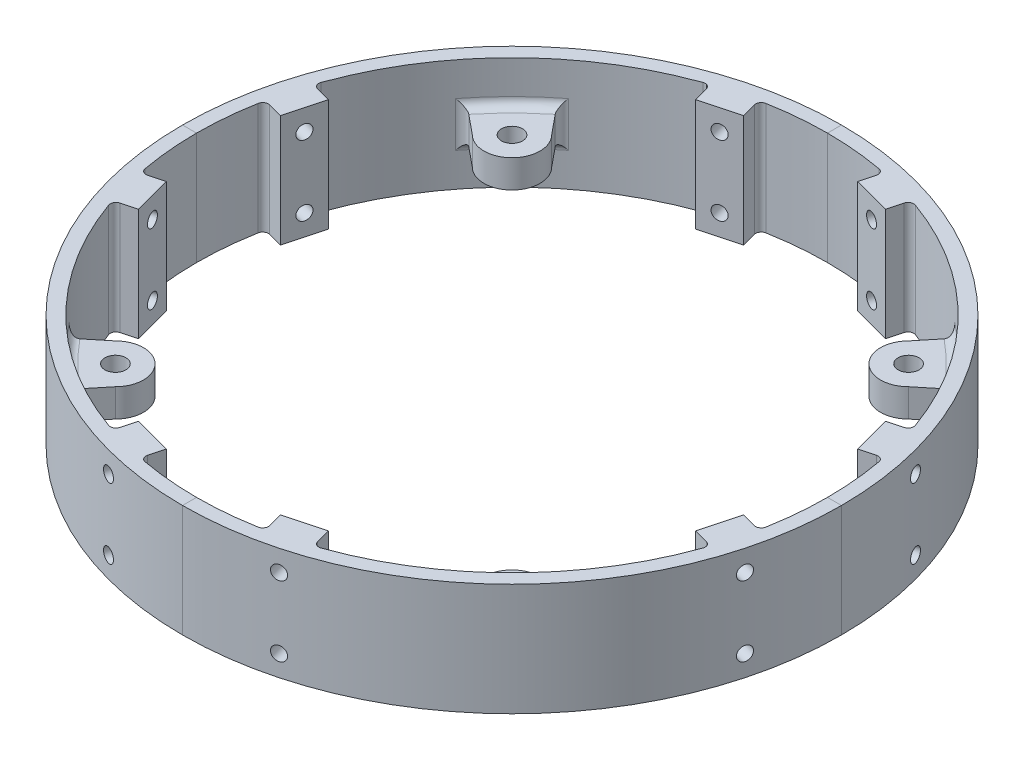
SolidWorks part; units mm, degrees
material "6061-T6 (SS)"
ref_plane "Front Plane" through (0, 0, 0) normal (0, 0, 1) x (1, 0, 0)
ref_plane "Top Plane" through (0, 0, 0) normal (0, 1, 0) x (1, 0, 0)
ref_plane "Right Plane" through (0, 0, 0) normal (1, 0, 0) x (0, 0, -1)
ref_axis "Axis of Revolution" through (0, -27.94, 0) along (0, 1, 0)
sketch "Sketch1" plane through (0, 0, 0) normal (0, 1, 0) x (1, 0, 0)
  line L0 (0, 149.225) -> (0, 0) construction
  line L1 (0, 0) -> (136.525, 0) construction
  line L2 (0, 0) -> (166.5143, 166.5143) construction
  line L3 (-617.3042, 796.9093) -> (89.8026, 89.8026) construction
  line L6 (0, 0) -> (51.1159, 190.7673) construction
  line L7 (0, 0) -> (78.0838, 135.2452) construction
  line L8 (101.0279, 101.0279) -> (93.1702, 93.1702)
  line L9 (86.435, 86.435) -> (80.8223, 80.8223)
  line L10 (80.8223, 98.7828) -> (62.9798, 109.0842) construction
  line L11 (80.8223, 98.7828) -> (90.4738, 110.5791)
  arc A10 (0, 149.225) -> (149.225, 0) centre (0, 0) cw construction
  arc A12 (93.1702, 93.1702) -> (86.435, 86.435) centre (89.8026, 89.8026) ccw
  arc A14 (0, 142.875) -> (142.875, 0) centre (0, 0) cw construction
  arc A15 (80.8223, 80.8223) -> (80.8223, 98.7828) centre (89.8026, 89.8026) cw
  arc A20 (71.4375, 123.7334) -> (101.0279, 101.0279) centre (0, 0) cw
  ellipse E0 centre (62.9798, 109.0842) end of major axis (80.8223, 98.7828) minor radius 16.9154 (71.4375, 123.7334) -> (80.8223, 98.7828) cw
  point P9 (74.6125, 129.2326)
  point P13 (71.4375, 123.7334)
  point P24 (80.8223, 80.8223)
  point P80 (0, 0)
  dimension "D8" = 9.525
  dimension "D1" = 149.225
  dimension "D3" = 127
  dimension "D4" = 45
  dimension "D5" = 12.7
  dimension "D2" = 30
  dimension "D6" = 15
  dimension "D7" = 6.35
extrude "Half of a Rod Holder (0.375\" Clearance)" add sketch "Sketch1" along normal blind 6.35 and the other way blind 6.35 contours L9 A12 region at (87.4048, 0, -96.8752)
mirror "Mirror Rod Holder" about plane through (0, -6.35, 0) normal (-0.7071, 0, -0.7071) of bodies 104
sketch "Sketch2" plane through (0, 0, 0) normal (0, 1, 0) x (1, 0, 0)
  line L2 (0, 0) -> (142.875, 0) construction
  line L3 (0, 0) -> (0, 142.875) construction
  line L4 (0, 142.875) -> (0, 149.225)
  line L5 (142.875, 0) -> (149.225, 0)
  arc A0 (149.225, 0) -> (0, 149.225) centre (0, 0) ccw
  arc A1 (142.875, 0) -> (0, 142.875) centre (0, 0) ccw
  dimension "D2" = 298.45
  dimension "D1" = 6.35
extrude "Quarter of Airframe Interface" add sketch "Sketch2" along normal blind 25.4 and the other way blind 25.4
fillet "Fillet for Rod Holder" radius 3.81 4 edges at (110.5791, 0, -90.4738) (101.0279, -6.35, -101.0279) (101.0279, 6.35, -101.0279) (90.4738, 0, -110.5791)
sketch "Sketch3" plane through (0, 0, 0) normal (0, 1, 0) x (1, 0, 0)
  line L0 (89.8026, 89.8026) -> (0, 0) construction
  line L2 (0, 0) -> (-146.317, -39.2055) construction
  line L4 (130.7238, 25.8237) -> (126.122, 42.9979)
  line L5 (126.122, 42.9979) -> (135.4383, 45.4942)
  line L6 (130.7238, 25.8237) -> (140.0401, 28.32)
  circle A9 centre (0, 0) radius 142.875 construction
  circle A10 centre (0, 0) radius 149.225 construction
  arc A11 (140.0401, 28.32) -> (135.4383, 45.4942) centre (0, 0) ccw
  circle A12 centre (89.8026, 89.8026) radius 4.7625 construction
  circle A16 centre (89.8026, 89.8026) radius 4.7625
  point P30 (128.4229, 34.4108)
  point P32 (144.1403, 38.6223)
  dimension "D3" = 17.78
  dimension "D4" = 16.2719
  dimension "D1" = 30
extrude "Radial Bolt Holder" add sketch "Sketch3" along normal up to surface (25.4 mm away) and the other way up to surface (25.4 mm away) contours L6 L5 | L4 L6 L5 region at (133.1705, 0, -35.6829) up to face at (88.149, 25.4, -88.149) other way up to face at (88.149, -25.4, -88.149)
sketch "Sketch4" plane through (128.4229, 0, -34.4108) normal (-0.9659, 0, 0.2588) x (0.2588, 0, 0.9659)
  line L0 (8.89, 25.4) -> (-8.89, 25.4) construction
  line L8 (-8.89, 6.35) -> (8.89, 6.35)
  line L9 (-8.89, 0) -> (8.89, 0) construction
  line L12 (-8.89, 25.4) -> (-8.89, -25.4) construction
  line L13 (-8.89, 25.4) -> (8.89, 6.35) construction
  line L14 (8.89, 25.4) -> (-8.89, 6.35) construction
  circle A0 centre (0, 15.875) radius 3.175
  circle A1 centre (0, -15.875) radius 3.175
  point P12 (-8.89, 0)
  dimension "D1" = 6.35
  dimension "D2" = 19.05
extrude "Radial Hole Cuts" cut sketch "Sketch4" against normal through all contours A1 | A0 region at (128.4229, -15.875, -34.4108)
ref_plane "Reflection Plane" through (0, 0, 0) normal (-0.7071, 0, -0.7071) x (-0.7071, 0, 0.7071)
mirror "Mirror Radial Bolt Holder" about plane through (0, 0, 0) normal (-0.7071, 0, -0.7071) of "Radial Hole Cuts", "Radial Bolt Holder"
fillet "Fillet for Radial Bolt Holders" radius 2.54 4 edges at (45.4942, 0, -135.4383) (28.32, 0, -140.0401) (135.4383, 0, -45.4942) (140.0401, 0, -28.32)
pattern_circular "CirPattern1" count 4 over 360 about axis through (0, -27.94, 0) along (0, 1, 0) of bodies 160
equation "\"Rocket Radius\"=6"
equation "\"Avionics Threaded Rod Diameter\"= 0.375in"
equation "\"D8@Sketch1\"=\"Avionics Threaded Rod Diameter\""
equation "\"Rocket Diameter\"= 12"
equation "\"D2@Sketch2\"=\"Rocket Diameter\"-(2*\"Airframe Thickness\")"
equation "\"Airframe Thickness\"= 0.125"
equation "\"D1@Sketch1\"=\"Rocket Radius\"-\"Airframe Thickness\""
equation "\"Bolt Flange Diameter\"= 19 / 32in"
equation "\"Bolt Height\"= 15 / 64in"
equation "\"D4@Sketch3\"=1-(\"Bolt Height\"+\"Airframe Thickness\")"
equation "\"Bolt Diameter\"=0.25"
equation "\"D1@Sketch4\"=\"Bolt Diameter\""
